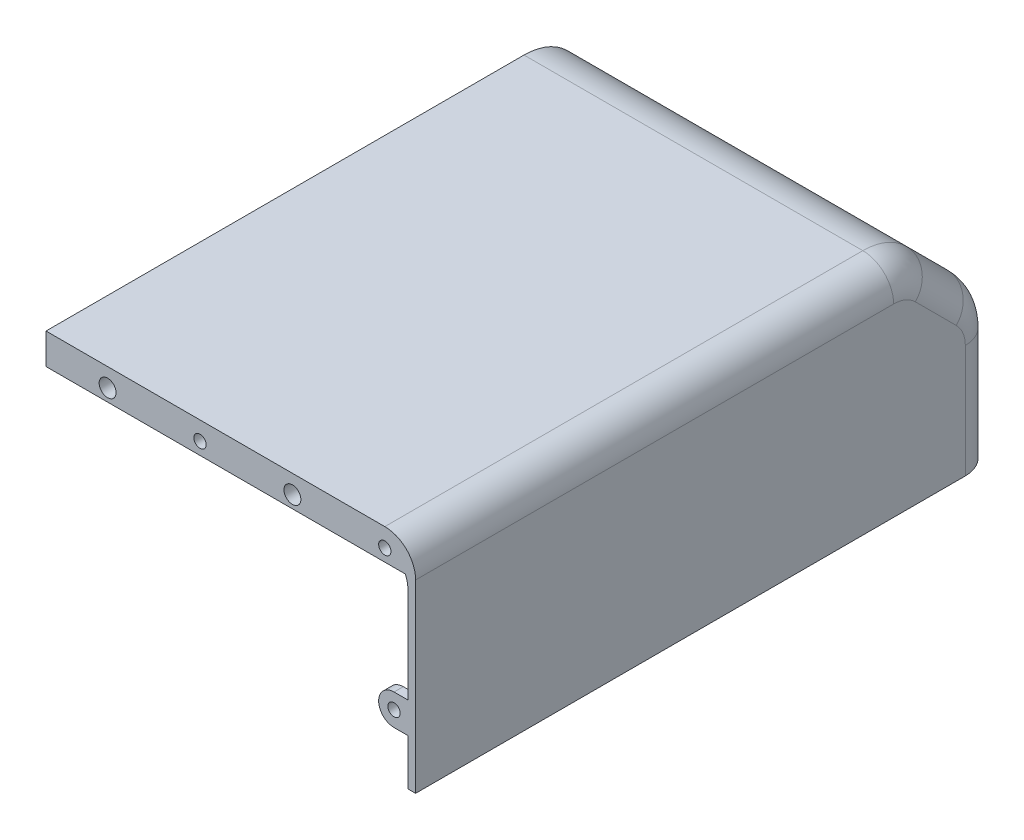
SolidWorks part; units mm, degrees
ref_plane "Alzado" through (0, 0, 0) normal (0, 0, 1) x (1, 0, 0)
ref_plane "Planta" through (0, 0, 0) normal (0, 1, 0) x (1, 0, 0)
ref_plane "Vista lateral" through (0, 0, 0) normal (1, 0, 0) x (0, 0, -1)
sketch "Croquis1" plane through (0, 0, 0) normal (1, 0, 0) x (0, 0, -1)
  line L0 (-210, 0) -> (210, 0)
  line L2 (21.5278, 70) -> (185, 70)
  line L3 (-210, 0) -> (-210, 20)
  line L4 (-210, 20) -> (-109.6319, 150.4846)
  line L5 (210, 0) -> (210, 45)
  line L6 (210, 45) -> (185, 70)
  line L7 (21.5278, 70) -> (21.5278, 75)
  line L8 (21.5278, 75) -> (-28.7753, 148.2935)
  arc A0 (-28.7753, 148.2935) -> (-109.6319, 150.4846) centre (-70, 120) ccw
  circle A1 centre (-70, 120) radius 13
  arc A3 (-109.6319, 150.4846) -> (-28.7753, 148.2935) centre (-70, 120) ccw construction
  point P3 (0, 0)
  dimension "D4" = 100
  dimension "D5" = 26
  dimension "D1" = 420
  dimension "D2" = 120
  dimension "D3" = 70
  dimension "D6" = 20
  dimension "D7" = 70
  dimension "D8" = 45
  dimension "D9" = 50.3031
  dimension "D10" = 45
  dimension "D11" = 5
extrude "Saliente-Extruir1" add sketch "Croquis1" against normal blind 120
sketch "Croquis2" plane through (-120, 0, 0) normal (-1, 0, 0) x (0, 0, 1)
  line L10 (106.4613, 148.0459) -> (206, 18.6396)
  line L11 (-206, 0) -> (-206, 43.3431)
  line L12 (210, 0) -> (-210, 0) construction
  line L13 (-206, 43.3431) -> (-183.3431, 66)
  line L14 (-183.3431, 66) -> (-37.5278, 66)
  line L15 (-37.5278, 66) -> (-37.5278, 60)
  line L16 (-37.5278, 60) -> (-17.5278, 60)
  line L17 (-17.5278, 60) -> (-17.5278, 73.7594)
  line L18 (-17.5278, 73.7594) -> (32.0733, 146.03)
  line L19 (-21.5278, 75) -> (28.7753, 148.2935) construction
  line L20 (-185, 70) -> (-21.5278, 70) construction
  line L21 (-210, 45) -> (-185, 70) construction
  line L22 (-210, 0) -> (-210, 45) construction
  line L23 (-21.5278, 70) -> (-21.5278, 75) construction
  line L24 (206, 18.6396) -> (206, 0)
  line L25 (206, 0) -> (-206, 0)
  line L26 (109.6319, 150.4846) -> (210, 20) construction
  line L27 (210, 20) -> (210, 0) construction
  arc A3 (106.4613, 148.0459) -> (32.0733, 146.03) centre (70, 120) ccw
  arc A4 (106.4613, 148.0459) -> (32.0733, 146.03) centre (70, 120) ccw
  dimension "D1" = 10
  dimension "D3" = 4
  dimension "D4" = 4
  dimension "D5" = 4
  dimension "D6" = 20
  dimension "D7" = 4
  dimension "D8" = 4
  dimension "D2" = 4
extrude "Cortar-Extruir1" cut sketch "Croquis2" against normal offset from surface (117.5 mm away) 2.5 up to face at (0, 120, 57)
fillet "Redondeo1" radius 20 6 edges at (-60, 45, -210) (-60, 70, -185) (-60, 20, 210) (-61.25, 18.6396, 206) (-61.25, 66, -183.3431) (-61.25, 43.3431, -206)
sketch "Croquis3" plane through (0, 0, -21.5278) normal (0, 0, -1) x (-1, 0, 0)
  line L0 (185, 195) -> (-65, 195)
  line L1 (185, 195) -> (185, -55)
  line L2 (185, -55) -> (-65, -55)
  line L3 (-65, 195) -> (-65, -55)
  line L4 (185, 195) -> (-65, -55) construction
  line L5 (185, -55) -> (-65, 195) construction
  line L6 (120, 70) -> (0, 70) construction
  point P0 (60, 70)
  dimension "D1" = 250
  dimension "D2" = 250
extrude "Cortar-Extruir2" cut sketch "Croquis3" against normal through all
sketch "Croquis6" plane through (-120, 0, 0) normal (-1, 0, 0) x (0, 0, 1)
  line L20 (-23.0278, 61.5) -> (-23.0278, 68.5)
  line L21 (-23.0278, 61.5) -> (-23.0278, 68.5)
  line L22 (-36.0278, 61.5) -> (-23.0278, 61.5)
  line L23 (-23.0278, 68.5) -> (-176.7157, 68.5)
  line L24 (-23.0278, 68.5) -> (-176.7157, 68.5)
  line L25 (-189.7972, 63.0815) -> (-203.0815, 49.7972)
  line L26 (-189.7972, 63.0815) -> (-203.0815, 49.7972)
  line L27 (-208.5, 1.5) -> (-207.5, 1.5)
  line L28 (-208.5, 36.7157) -> (-208.5, 1.5)
  line L29 (-208.5, 36.7157) -> (-208.5, 1.5)
  line L32 (-36.0278, 61.5) -> (-23.0278, 61.5)
  line L37 (-208.5, 1.5) -> (-207.5, 1.5)
  line L40 (-207.5, 1.5) -> (-207.5, 35.0589)
  line L41 (-207.5, 1.5) -> (-207.5, 35.0589)
  line L42 (-201.2028, 50.2617) -> (-190.2617, 61.2028)
  line L43 (-201.2028, 50.2617) -> (-190.2617, 61.2028)
  line L44 (-175.0589, 67.5) -> (-36.0278, 67.5)
  line L45 (-175.0589, 67.5) -> (-36.0278, 67.5)
  line L46 (-36.0278, 67.5) -> (-36.0278, 61.5)
  line L47 (-36.0278, 67.5) -> (-36.0278, 61.5)
  arc A9 (-176.7157, 68.5) -> (-189.7972, 63.0815) centre (-176.7157, 50) ccw
  arc A10 (-176.7157, 68.5) -> (-189.7972, 63.0815) centre (-176.7157, 50) ccw
  arc A11 (-203.0815, 49.7972) -> (-208.5, 36.7157) centre (-190, 36.7157) ccw
  arc A12 (-203.0815, 49.7972) -> (-208.5, 36.7157) centre (-190, 36.7157) ccw
  arc A13 (-201.2028, 50.2617) -> (-207.5, 35.0589) centre (-186, 35.0589) ccw
  arc A14 (-201.2028, 50.2617) -> (-207.5, 35.0589) centre (-186, 35.0589) ccw
  arc A20 (-175.0589, 67.5) -> (-190.2617, 61.2028) centre (-175.0589, 46) ccw
  arc A21 (-175.0589, 67.5) -> (-190.2617, 61.2028) centre (-175.0589, 46) ccw
  dimension "D1" = 1.5
extrude "Cortar-Extruir4" cut sketch "Croquis6" against normal blind 5
sketch "Croquis7" plane through (0, 0, -21.5278) normal (0, 0, 1) x (1, 0, 0)
  line L4 (-120, 60) -> (-2.5, 60) construction
  circle A0 centre (-40, 64) radius 2.75
  circle A1 centre (-100, 64) radius 2.75
  circle A2 centre (-70, 64) radius 2
  circle A3 centre (-10, 64) radius 2
  dimension "D1" = 5.5
  dimension "D2" = 5.5
  dimension "D4" = 4
  dimension "D5" = 4
  dimension "D3" = 60
  dimension "D7" = 30
  dimension "D8" = 30
  dimension "D9" = 4
  dimension "D13" = 40
extrude "Cortar-Extruir5" cut sketch "Croquis7" against normal blind 6
fillet "Redondeo5" radius 10 10 edges at (0, 18.3579, -210) (0, 44.3694, -208.4776) (0, 57.5, -197.5) (0, 68.4776, -184.3694) (0, 70, -99.1218) (-2.5, 17.5294, -206) (-2.5, 42.7125, -204.4776) (-2.5, 54.6716, -194.6716) (-2.5, 64.4776, -182.7125) (-2.5, 66, -106.2933)
sketch "Croquis8" plane through (0, 0, -210) normal (0, 0, -1) x (-1, 0, 0)
  line L0 (112, 3) -> (108, 3)
  line L1 (112, 3) -> (112, 33)
  line L2 (112, 33) -> (108, 33)
  line L3 (108, 3) -> (108, 33)
  line L4 (112, 3) -> (108, 33) construction
  line L5 (112, 33) -> (108, 3) construction
  line L6 (102.9, 3) -> (102.9, 33)
  line L7 (102.9, 3) -> (98.9, 3)
  line L8 (98.9, 3) -> (98.9, 33)
  line L9 (102.9, 33) -> (98.9, 33)
  line L10 (93.8, 3) -> (93.8, 33)
  line L11 (93.8, 3) -> (89.8, 3)
  line L12 (89.8, 3) -> (89.8, 33)
  line L13 (93.8, 33) -> (89.8, 33)
  line L14 (84.7, 3) -> (84.7, 33)
  line L15 (84.7, 3) -> (80.7, 3)
  line L16 (80.7, 3) -> (80.7, 33)
  line L17 (84.7, 33) -> (80.7, 33)
  line L18 (75.6, 3) -> (75.6, 33)
  line L19 (75.6, 3) -> (71.6, 3)
  line L20 (71.6, 3) -> (71.6, 33)
  line L21 (75.6, 33) -> (71.6, 33)
  line L22 (66.5, 3) -> (66.5, 33)
  line L23 (66.5, 3) -> (62.5, 3)
  line L24 (62.5, 3) -> (62.5, 33)
  line L25 (66.5, 33) -> (62.5, 33)
  line L26 (57.4, 3) -> (57.4, 33)
  line L27 (57.4, 3) -> (53.4, 3)
  line L28 (53.4, 3) -> (53.4, 33)
  line L29 (57.4, 33) -> (53.4, 33)
  line L30 (48.3, 3) -> (48.3, 33)
  line L31 (48.3, 3) -> (44.3, 3)
  line L32 (44.3, 3) -> (44.3, 33)
  line L33 (48.3, 33) -> (44.3, 33)
  line L34 (39.2, 3) -> (39.2, 33)
  line L35 (39.2, 3) -> (35.2, 3)
  line L36 (35.2, 3) -> (35.2, 33)
  line L37 (39.2, 33) -> (35.2, 33)
  line L38 (30.1, 3) -> (30.1, 33)
  line L39 (30.1, 3) -> (26.1, 3)
  line L40 (26.1, 3) -> (26.1, 33)
  line L41 (30.1, 33) -> (26.1, 33)
  line L42 (21, 3) -> (21, 33)
  line L43 (21, 3) -> (17, 3)
  line L44 (17, 3) -> (17, 33)
  line L45 (21, 33) -> (17, 33)
  line L46 (120, 0) -> (10, 0) construction
  line L47 (120, 0) -> (120, 36.7157) construction
  point P0 (110, 18)
  dimension "D1" = 4
  dimension "D2" = 30
  dimension "D3" = 95
  dimension "D4" = 18
  dimension "D5" = 10
  dimension "D6" = 5.1
  dimension "D7" = 5.1
  dimension "D8" = 5.1
  dimension "D9" = 5.1
  dimension "D10" = 5.1
  dimension "D11" = 5.1
  dimension "D12" = 5.1
  dimension "D13" = 5.1
  dimension "D14" = 5.1
extrude "Cortar-Extruir6" cut sketch "Croquis8" against normal blind 15
fillet "Redondeo6" radius 2 44 edges at (-21, 3, -208) (-17, 3, -208) (-17, 33, -208) (-30.1, 3, -208) (-26.1, 3, -208) (-26.1, 33, -208) (-30.1, 33, -208) (-39.2, 3, -208) (-35.2, 3, -208) (-35.2, 33, -208) (-39.2, 33, -208) (-48.3, 3, -208) (-44.3, 3, -208) (-44.3, 33, -208) (-48.3, 33, -208) (-57.4, 3, -208) (-53.4, 3, -208) (-53.4, 33, -208) (-57.4, 33, -208) (-66.5, 3, -208) (-62.5, 3, -208) (-62.5, 33, -208) (-66.5, 33, -208) (-75.6, 3, -208) (-71.6, 3, -208) (-71.6, 33, -208) (-75.6, 33, -208) (-84.7, 3, -208) (-80.7, 3, -208) (-80.7, 33, -208) (-84.7, 33, -208) (-93.8, 3, -208) (-89.8, 3, -208) (-89.8, 33, -208) (-93.8, 33, -208) (-102.9, 3, -208) (-98.9, 3, -208) (-98.9, 33, -208) (-102.9, 33, -208) (-112, 33, -208) (-112, 3, -208) (-108, 3, -208) (-108, 33, -208) (-21, 33, -208)
sketch "Croquis9" plane through (0, 0, 0) normal (0, -1, 0) x (1, 0, 0)
  line L0 (-2.5, -125) -> (-5, -125)
  line L1 (-2.5, -135) -> (-5, -135)
  line L2 (-2.5, -37.5278) -> (-2.5, -175.0589) construction
  line L3 (-2.5, -125) -> (-2.5, -135)
  line L4 (-2.5, -196) -> (-2.5, -21.5278) construction
  line L5 (0, -21.5278) -> (0, -200) construction
  circle A0 centre (-5, -130) radius 2.25
  arc A1 (-5, -135) -> (-5, -125) centre (-5, -130) cw
  dimension "D2" = 4.5
  dimension "D1" = 10
  dimension "D3" = 5
  dimension "D4" = 130
extrude "Saliente-Extruir3" add sketch "Croquis9" against normal blind 6
sketch "Croquis10" plane through (-120, 0, 0) normal (-1, 0, 0) x (0, 0, 1)
  line L0 (-210, 0) -> (-216, 0)
  line L1 (-216, 10) -> (-210, 10)
  line L2 (-210, 0) -> (-210, 36.7157) construction
  line L3 (-210, 10) -> (-210, 0)
  line L4 (-206, 35.0589) -> (-206, 0) construction
  arc A0 (-216, 0) -> (-216, 10) centre (-216, 5) cw
  circle A1 centre (-216, 5) radius 1.5
  dimension "D3" = 3
  dimension "D1" = 10
  dimension "D2" = 10
extrude "Saliente-Extruir4" add sketch "Croquis10" against normal blind 3
sketch "Croquis11" plane through (0, 0, -21.5278) normal (0, 0, 1) x (1, 0, 0)
  line L0 (-2.5, 15) -> (-7, 15)
  line L1 (-2.5, 35.0589) -> (-2.5, 0) construction
  line L2 (-7, 25) -> (-2.5, 25)
  line L3 (-2.5, 25) -> (-2.5, 15)
  line L4 (0, 60) -> (0, 0) construction
  arc A0 (-7, 15) -> (-7, 25) centre (-7, 20) cw
  circle A1 centre (-7, 20) radius 2
  dimension "D1" = 4
  dimension "D2" = 10
  dimension "D3" = 20
  dimension "D4" = 7
extrude "Saliente-Extruir5" add sketch "Croquis11" against normal blind 3
